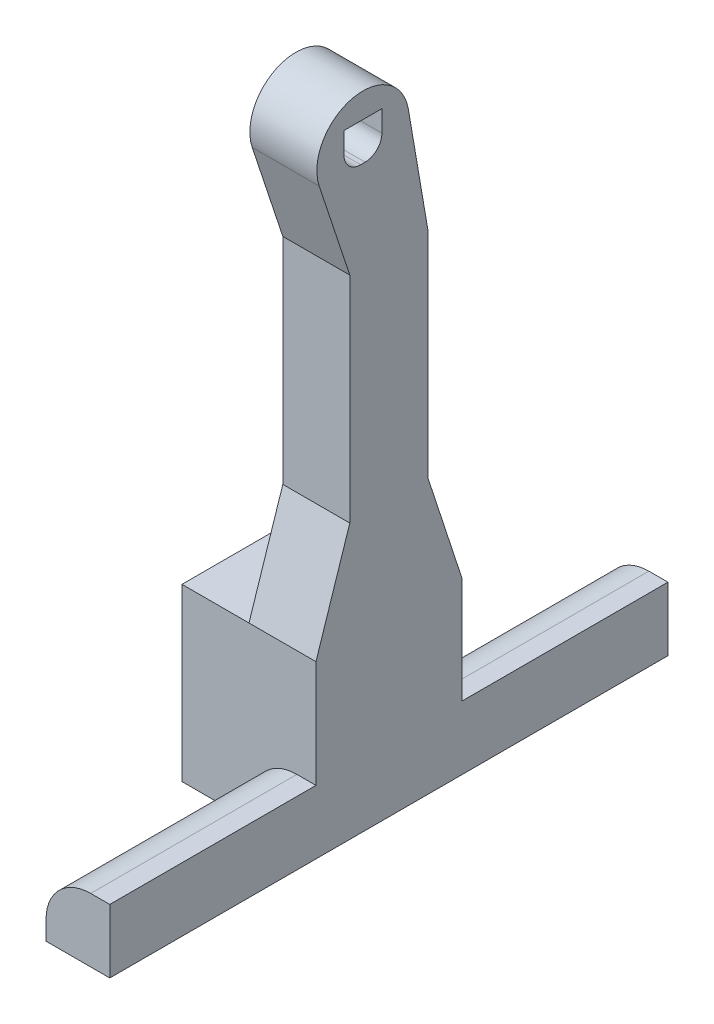
SolidWorks part; units mm, degrees
ref_plane "Front Plane" through (0, 0, 0) normal (0, 0, 1) x (1, 0, 0)
ref_plane "Top Plane" through (0, 0, 0) normal (0, 1, 0) x (1, 0, 0)
ref_plane "Right Plane" through (0, 0, 0) normal (1, 0, 0) x (0, 0, -1)
sketch "Sketch1" plane through (0, 0, 0) normal (1, 0, 0) x (0, 0, -1)
  line L0 (-3, 9.82) -> (-3, 0)
  line L1 (-3, 0) -> (-6.5301, 0)
  line L2 (-6.5301, 0) -> (-6.5301, 9.82)
  line L3 (-6.5301, 15.3053) -> (-3.4983, 24.5417)
  line L4 (-3.4983, 24.5417) -> (-3.4983, 43.7787)
  line L5 (0, 0) -> (0, 50000) construction
  line L6 (3.4983, 24.5417) -> (3.4983, 43.7787)
  line L7 (6.5301, 15.3053) -> (3.4983, 24.5417)
  line L8 (6.5301, 0) -> (6.5301, 9.82)
  line L9 (3, 0) -> (6.5301, 0)
  line L10 (3, 9.82) -> (3, 0)
  line L11 (-3, 9.82) -> (3, 9.82)
  line L12 (-2.5244, 52.0529) -> (-2.1244, 52.0529) construction
  line L13 (-2.5244, 53.3529) -> (-2.1244, 53.3529) construction
  line L14 (-3.8244, 55.0529) -> (-3.8244, 53.3529) construction
  line L15 (-0.8244, 53.3529) -> (-0.8244, 55.0529) construction
  line L16 (-0.8244, 55.0529) -> (-3.8244, 55.0529) construction
  line L17 (-3.8244, 55.0529) -> (-0.8244, 55.0529) construction
  line L18 (-2.5244, 52.0529) -> (-2.1244, 52.0529) construction
  line L19 (-3.8244, 55.0529) -> (-3.8244, 53.3529) construction
  line L20 (-0.8244, 53.3529) -> (-0.8244, 55.0529) construction
  line L21 (-0.8244, 55.0529) -> (-3.8244, 55.0529) construction
  line L22 (-3.8244, 55.0529) -> (-0.8244, 55.0529)
  line L23 (-3.4983, 43.7787) -> (-6.2409, 52.0551)
  line L24 (3.4983, 43.7787) -> (1.7425, 54.0483)
  line L25 (6.5301, 9.82) -> (6.5301, 15.3053)
  line L26 (-6.5301, 9.82) -> (-6.5301, 15.3053)
  line L27 (-6.5301, 9.82) -> (-3, 9.82)
  line L28 (3, 9.82) -> (6.5301, 9.82)
  line L29 (3, 0) -> (-3, 0)
  line L30 (6.5301, 15.3053) -> (-6.5301, 15.3053)
  line L31 (-0.6244, 55.2529) -> (-4.0244, 55.2529)
  line L32 (-4.0244, 55.2529) -> (-4.0244, 53.3529)
  line L33 (-2.5244, 51.8529) -> (-2.1244, 51.8529)
  line L34 (-0.6244, 53.3529) -> (-0.6244, 55.2529)
  line L35 (-25, 12.1535) -> (-25, -1.9655) construction
  line L36 (25, 12.1535) -> (25, -1.9655) construction
  arc A0 (-2.1244, 52.0529) -> (-0.8244, 53.3529) centre (-2.1244, 53.3529) ccw construction
  arc A1 (-3.8244, 53.3529) -> (-2.5244, 52.0529) centre (-2.5244, 53.3529) ccw construction
  arc A2 (-2.1244, 52.0529) -> (-0.8244, 53.3529) centre (-2.1244, 53.3529) ccw construction
  arc A3 (-3.8244, 53.3529) -> (-2.5244, 52.0529) centre (-2.5244, 53.3529) ccw construction
  arc A4 (-6.2409, 52.0551) -> (1.7425, 54.0483) centre (-2.3244, 53.3529) cw
  arc A5 (-4.0244, 53.3529) -> (-2.5244, 51.8529) centre (-2.5244, 53.3529) ccw
  arc A6 (-2.1244, 51.8529) -> (-0.6244, 53.3529) centre (-2.1244, 53.3529) ccw
  dimension "D3" = 0.2
  dimension "D1" = 6
  dimension "D2" = 9.82
  dimension "D4" = 25
extrude "Boss-Extrude2" add sketch "Sketch1" against normal blind 6 contours L28 L10 L9 L8 | L27 L2 L1 L0 | L25 L30 L26 L27 L11 L28 region at (0, 12.5626, 0) region at (0, 4.91, 4.7651) region at (0, 4.91, -4.7651)
extrude "Boss-Extrude3" add sketch "Sketch1<4>" along normal blind 6 contours L29 L10 L11 L0 | L27 L2 L1 L0 | L28 L10 L9 L8 | L25 L30 L26 L27 L11 L28 | A4 L23 L4 L3 L30 L7 L6 L24 A3 L19 L21 L20 A2 L18 region at (0, 4.91, 0) region at (0, 12.5626, 0) region at (0, 4.91, 4.7651) region at (0, 4.91, -4.7651) region at (0, 34.3885, 0.4068)
sketch "Sketch1<4>" plane through (0, 0, 0) normal (1, 0, 0) x (0, 0, -1) same geometry as "Sketch1"
sketch "Sketch4" plane through (0, 0, 6.5301) normal (0, 0, 1) x (1, 0, 0)
  line L1 (6, 0) -> (0.2928, 0)
  line L2 (6, 0) -> (6, 5.7072)
  line L3 (6, 5.7072) -> (4.2928, 5.7072)
  line L4 (0.2928, 0) -> (0.2928, 1.7072)
  arc A0 (0.2928, 1.7072) -> (4.2928, 5.7072) centre (4.2928, 1.7072) cw
  dimension "D1" = 4
extrude "Boss-Extrude4" add sketch "Sketch4" along normal up to vertex (18.4699 mm away) and the other way up to vertex (31.5301 mm away) up to point (0, -1.9655, 25) other way up to point (0, -1.9655, -25)
